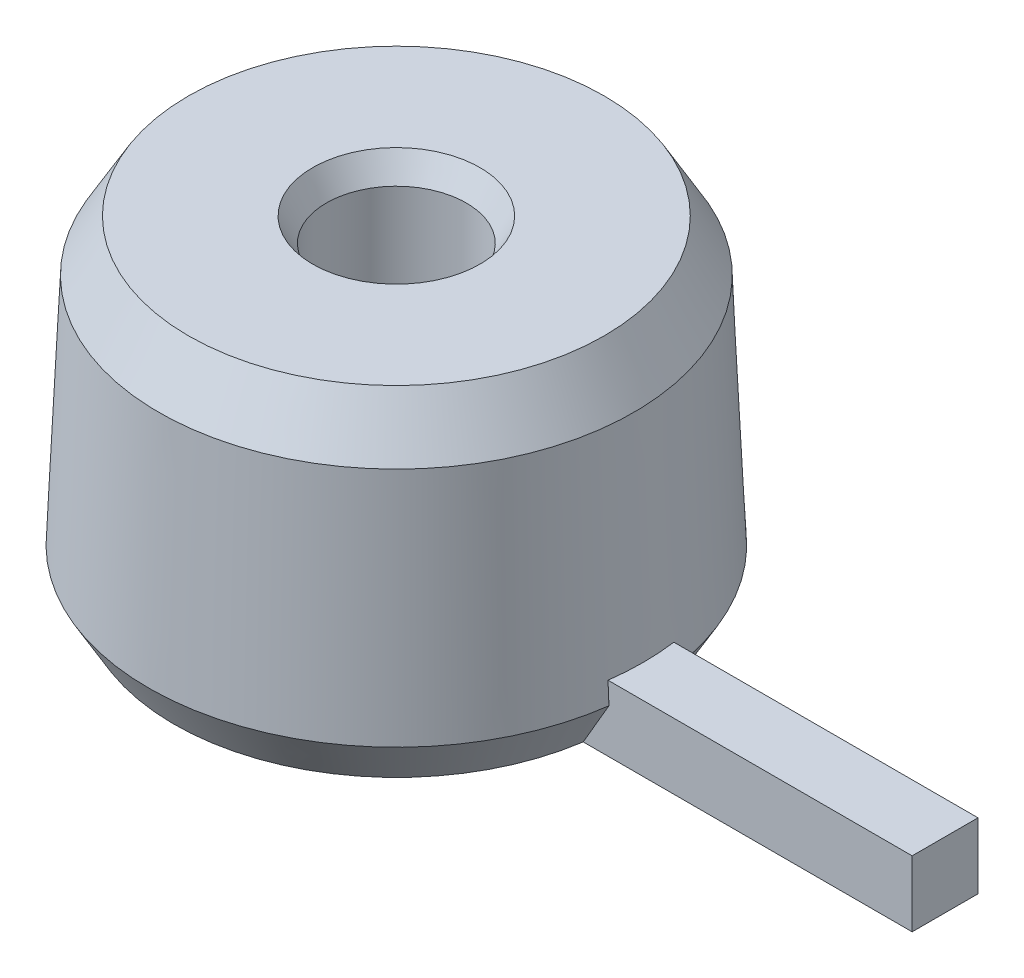
SolidWorks part; units mm, degrees
ref_plane "前视基准面" through (0, 0, 0) normal (0, 0, 1) x (1, 0, 0)
ref_plane "上视基准面" through (0, 0, 0) normal (0, 1, 0) x (1, 0, 0)
ref_plane "右视基准面" through (0, 0, 0) normal (1, 0, 0) x (0, 0, -1)
sketch "草图1" plane through (0, 0, 0) normal (0, 1, 0) x (1, 0, 0)
  circle A0 centre (0, 0) radius 9.1
  dimension "D1" = 18.2
extrude "凸台-拉伸1" add sketch "草图1" along normal blind 12 draft 2.5
sketch "草图2" plane through (0, 12, 0) normal (0, 1, 0) x (1, 0, 0)
  circle A0 centre (0, 0) radius 2.55
  dimension "D1" = 5.1
extrude "切除-拉伸1" cut sketch "草图2" against normal blind 8
sketch "草图3" plane through (0, 0, 0) normal (0, -1, 0) x (1, 0, 0)
  line L0 (7, 1.2) -> (7, -1.2)
  line L1 (7, -1.2) -> (20, -1.2)
  line L2 (20, -1.2) -> (20, 1.2)
  line L3 (20, 1.2) -> (7, 1.2)
  point P2 (7, 0)
  dimension "D1" = 2.4
  dimension "D2" = 7
  dimension "D3" = 13
extrude "凸台-拉伸2" add sketch "草图3" against normal blind 2.4
chamfer "倒角1" distance 0.5 angle 60 1 edges at (0, 12, 2.55) first distance on face at (0, 12, 2.55)
chamfer "倒角2" distance 1 angle 60 1 edges at (-9.1, 0, 0) first distance on face at (9.9801, 0, 0)
chamfer "倒角3" distance 1 angle 60 1 edges at (0, 12, 8.5761) first distance on face at (0, 12, 3.05)
